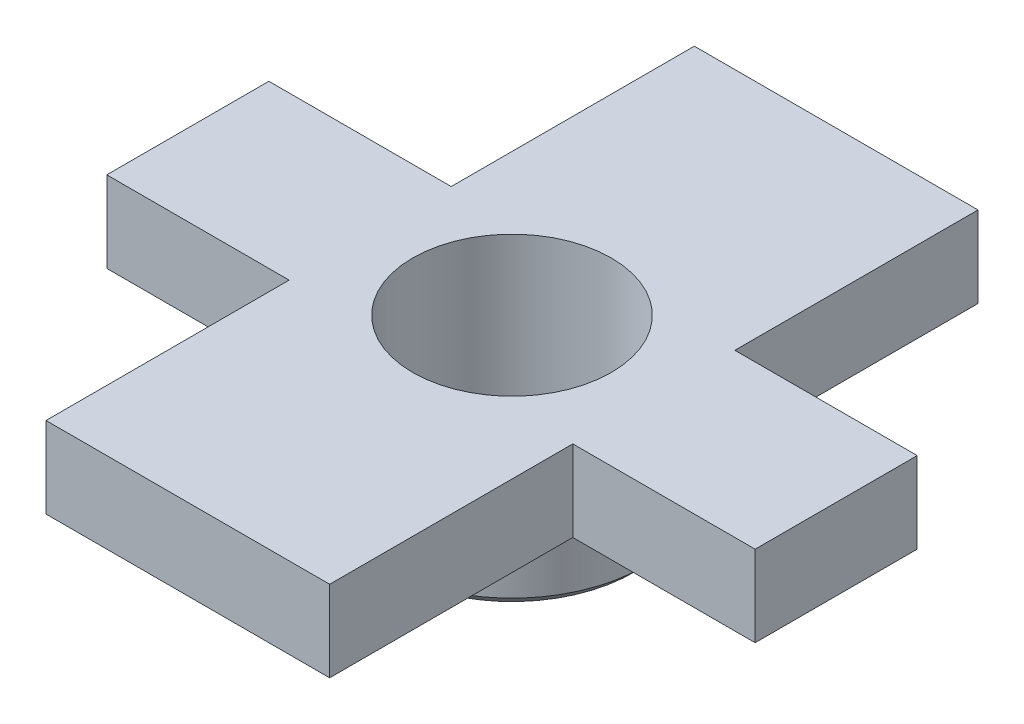
SolidWorks part; units mm, degrees
ref_plane "Ebene vorne" through (0, 0, 0) normal (0, 0, 1) x (1, 0, 0)
ref_plane "Ebene oben" through (0, 0, 0) normal (0, 1, 0) x (1, 0, 0)
ref_plane "Ebene rechts" through (0, 0, 0) normal (1, 0, 0) x (0, 0, -1)
sketch "Skizze4" plane through (0, 0, 0) normal (0, 1, 0) x (1, 0, 0)
  line L0 (-49.0844, 0) -> (52.7488, 0) construction
  line L1 (-55, 0) -> (55, 0) construction
  line L2 (0, 36.0148) -> (0, -34.5812) construction
  line L3 (0, -55) -> (0, 55) construction
  line L4 (-8, -2) -> (-8, 2)
  line L5 (-8, 2) -> (-3.5, 2)
  line L6 (-3.5, 2) -> (-3.5, 8)
  line L7 (-3.5, 8) -> (3.5, 8)
  line L8 (-3.5, -8) -> (3.5, -8)
  line L9 (-3.5, -2) -> (-3.5, -8)
  line L10 (-8, -2) -> (-3.5, -2)
  line L11 (8, -2) -> (3.5, -2)
  line L12 (3.5, -2) -> (3.5, -8)
  line L13 (3.5, 2) -> (3.5, 8)
  line L14 (8, 2) -> (3.5, 2)
  line L15 (8, -2) -> (8, 2)
  point P18 (-8, 0)
  point P21 (0, -8)
  point P22 (0, 8)
  point P24 (8, 0)
  dimension "D1" = 2
  dimension "D2" = 3.5
  dimension "D3" = 4.5
  dimension "D4" = 6
extrude "Grundplatte Kreuz " add sketch "Skizze4" along normal blind 2
sketch "Skizze11" plane through (0, 0, 0) normal (0, 1, 0) x (1, 0, 0)
  line L0 (5.8896, 0) -> (-5.2924, 0) construction
  line L1 (-1.1, 0) -> (1.1, 0) construction
  circle A0 centre (0, 0) radius 1.25
  dimension "D1" = 2.5
extrude "Mittelbohrung" cut sketch "Skizze11" along normal through all both and the other way through all
sketch "Skizze12" plane through (0, 0, 0) normal (0, -1, 0) x (1, 0, 0)
  line L0 (4.3451, 0) -> (-4.5305, 0) construction
  line L1 (1.1, 0) -> (-1.1, 0) construction
  circle A0 centre (0, 0) radius 3.25
  dimension "D1" = 6.5
extrude "Aufsatz-Linear austragen2" add sketch "Skizze12" along normal blind 2
chamfer "Fase1" distance 0.25 angle 45 1 edges at (0, -2, -3.25)
sketch "Skizze13" plane through (0, -2, 0) normal (0, -1, 0) x (1, 0, 0)
  circle A0 centre (0, 0) radius 2.45
  dimension "D1" = 4.9
extrude "Schnitt-Linear austragen1" cut sketch "Skizze13" against normal up to surface (4 mm away) up to face at (0, 2, 1.25)
